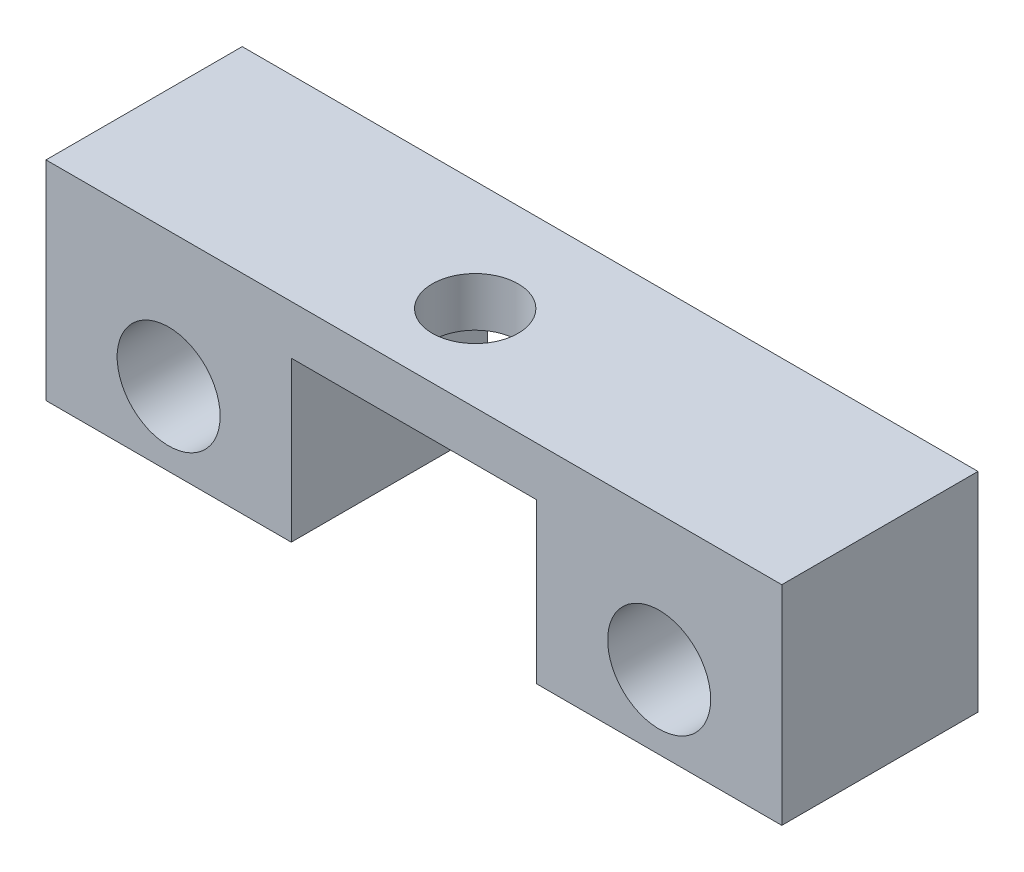
SolidWorks part; units mm, degrees
ref_plane "Front Plane" through (0, 0, 0) normal (0, 0, 1) x (1, 0, 0)
ref_plane "Top Plane" through (0, 0, 0) normal (0, 1, 0) x (1, 0, 0)
ref_plane "Right Plane" through (0, 0, 0) normal (1, 0, 0) x (0, 0, -1)
sketch "Sketch1" plane through (0, 0, 0) normal (0, 1, 0) x (1, 0, 0)
  line L0 (-1, -0.5) -> (-1, -4) construction
  line L5 (-15, 4) -> (15, 4)
  line L6 (-15, 4) -> (-15, -4)
  line L7 (-15, -4) -> (15, -4)
  line L8 (15, 4) -> (15, -4)
  line L9 (-15, 4) -> (15, -4) construction
  line L10 (-15, -4) -> (15, 4) construction
  line L11 (-1, 0) -> (0, 0) construction
  circle A0 centre (-1, -0.5) radius 1.75
  point P0 (0, 0)
  dimension "D3" = 3.5
  dimension "D1" = 30
  dimension "D2" = 8
  dimension "D4" = 3.5
  dimension "D5" = 1
extrude "Boss-Extrude1" add sketch "Sketch1" along normal blind 2
sketch "Sketch2" plane through (0, 0, 4) normal (0, 0, 1) x (1, 0, 0)
  line L0 (-10, -3.5) -> (10, -3.5) construction
  line L1 (-15, 0) -> (-5, 0)
  line L2 (-15, 0) -> (-15, -6.5)
  line L3 (-15, -6.5) -> (-5, -6.5)
  line L4 (-5, 0) -> (-5, -6.5)
  line L5 (15, 0) -> (5, 0)
  line L6 (15, 0) -> (15, -6.5)
  line L7 (15, -6.5) -> (5, -6.5)
  line L8 (5, 0) -> (5, -6.5)
  line L10 (-15, 2) -> (15, 2) construction
  line L11 (-15, 0) -> (15, 0) construction
  circle A0 centre (-10, -3.5) radius 2.1
  circle A1 centre (10, -3.5) radius 2.1
  point P12 (-10, 0)
  point P13 (10, 0)
  point P17 (0, -3.5)
  point P22 (0, 0)
  dimension "D1" = 4.2
  dimension "D2" = 4.2
  dimension "D3" = 5.5
  dimension "D4" = 6.5
  dimension "D5" = 20
extrude "Boss-Extrude2" add sketch "Sketch2" against normal up to surface (8 mm away) up to face at (0, 1, -4)
sketch "Sketch3" plane through (0, 0, 0) normal (0, -1, 0) x (1, 0, 0)
  line L1 (-2.7321, -2.5) -> (0.7321, -2.5) construction
  line L2 (0.7321, -2.5) -> (2.4641, 0.5) construction
  line L3 (2.4641, 0.5) -> (0.7321, 3.5) construction
  line L4 (0.7321, 3.5) -> (-2.7321, 3.5) construction
  line L5 (-2.7321, 3.5) -> (-4.4641, 0.5) construction
  line L6 (-4.4641, 0.5) -> (-2.7321, -2.5) construction
  circle A0 centre (-1, 0.5) radius 3 construction
  dimension "D1" = 6
sketch "Sketch4" plane through (0, 0, -4) normal (0, 0, -1) x (-1, 0, 0)
  line L8 (-15, 2) -> (-15, -6.5)
  line L9 (-15, -6.5) -> (-5, -6.5)
  line L10 (-5, -6.5) -> (-5, 0)
  line L11 (-5, 0) -> (5, 0)
  line L12 (5, 0) -> (5, -6.5)
  line L13 (5, -6.5) -> (15, -6.5)
  line L14 (15, -6.5) -> (15, 2)
  line L15 (15, 2) -> (-15, 2)
  line L16 (-15, 2) -> (-15, -6.5)
  line L17 (-15, -6.5) -> (-5, -6.5)
  line L18 (-5, -6.5) -> (-5, 0)
  line L19 (-5, 0) -> (5, 0)
  line L20 (5, 0) -> (5, -6.5)
  line L21 (5, -6.5) -> (15, -6.5)
  line L22 (15, -6.5) -> (15, 2)
  line L23 (15, 2) -> (-15, 2)
  dimension "D1" = 0
extrude "Boss-Extrude3" add sketch "Sketch4" against normal offset from surface (2 mm away) 6 up to face at (0, -2.75, 4)
